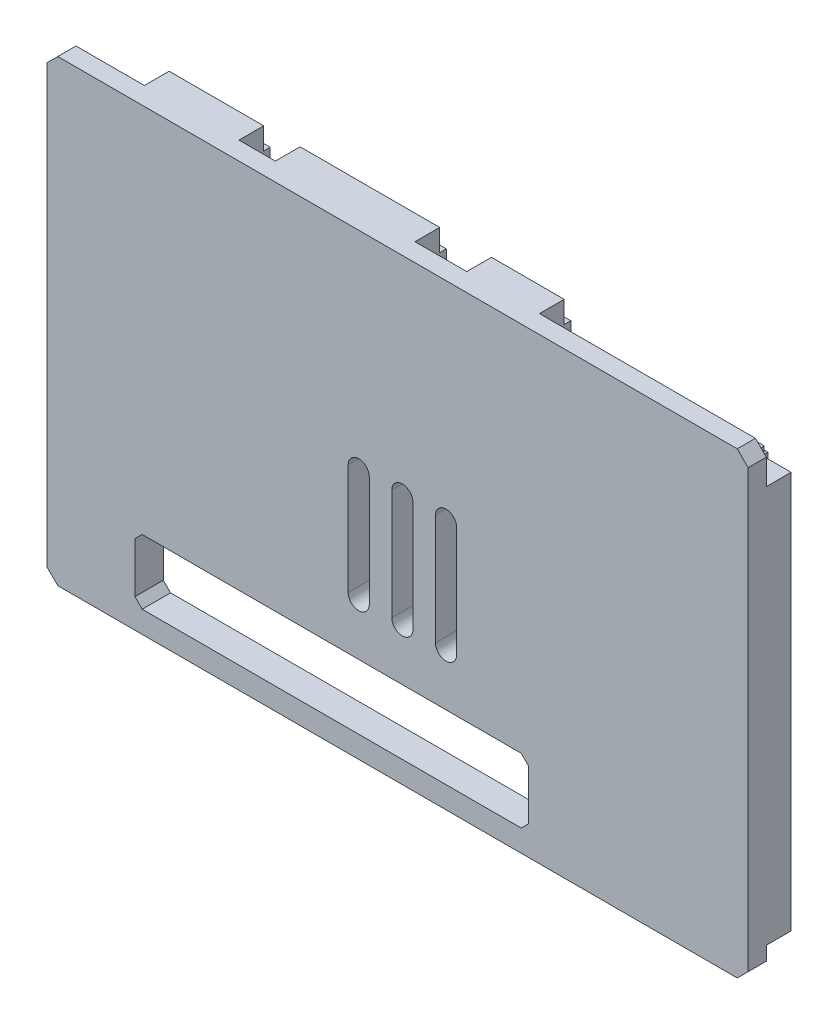
SolidWorks part; units mm, degrees
ref_plane "Front Plane" through (0, 0, 0) normal (0, 0, 1) x (1, 0, 0)
ref_plane "Top Plane" through (0, 0, 0) normal (0, 1, 0) x (1, 0, 0)
ref_plane "Right Plane" through (0, 0, 0) normal (1, 0, 0) x (0, 0, -1)
sketch "Sketch1" plane through (0, 0, 0) normal (0, 0, 1) x (1, 0, 0)
  line L1 (-38.1418, 30.0688) -> (58.2582, 30.0688)
  line L2 (-38.1418, 30.0688) -> (-38.1418, -32.9312)
  line L3 (-38.1418, -32.9312) -> (58.2582, -32.9312)
  line L4 (58.2582, 30.0688) -> (58.2582, -32.9312)
  line L5 (-36.4418, 28.3688) -> (56.5582, 28.3688)
  line L6 (-36.4418, 28.3688) -> (-36.4418, -31.2312)
  line L7 (-36.4418, -31.2312) -> (56.5582, -31.2312)
  line L8 (56.5582, 28.3688) -> (56.5582, -31.2312)
  line L9 (-31.6418, 27.0688) -> (55.2582, 27.0688)
  line L10 (-31.6418, 27.0688) -> (-31.6418, -29.9312)
  line L11 (-31.6418, -29.9312) -> (55.2582, -29.9312)
  line L12 (55.2582, 27.0688) -> (55.2582, -29.9312)
  dimension "D1" = 96.4
  dimension "D2" = 63
  dimension "D3" = 3
  dimension "D4" = 6.5
  dimension "D5" = 4.8
  dimension "D6" = 1.3
  dimension "D7" = 1.3
  dimension "D8" = 3
  dimension "D9" = 3
  dimension "D10" = 1.3
extrude "Boss-Extrude1" add sketch "Sketch1" along normal blind 2.5 contours L1 L4 L3 L2
extrude "Boss-Extrude2" add sketch "Sketch1<5>" against normal blind 1.4 contours L12 L9 L10 L11 | L8 L5 L6 L7 L9 L12 L11 L10 region at (10.0582, 27.2643, 0) region at (11.8082, -1.4312, 0)
sketch "Sketch1<5>" plane through (0, 0, 0) normal (0, 0, 1) x (1, 0, 0) same geometry as "Sketch1"
chamfer "Chamfer1" distance 1.5 angle 45 4 edges at (58.2582, 30.0688, 1.25) (-38.1418, 30.0688, 1.25) (-38.1418, -32.9312, 1.25) (58.2582, -32.9312, 1.25)
sketch "Sketch3" plane through (0, 0, -1.4) normal (0, 0, -1) x (-1, 0, 0)
  line L0 (36.4418, 28.3688) -> (36.4418, 28.1688)
  line L1 (36.4418, 28.3688) -> (36.4418, -31.2312) construction
  line L2 (36.4418, 28.1688) -> (36.4418, 5.3688)
  line L3 (36.4418, 5.3688) -> (36.4418, 4.9688)
  line L4 (36.4418, 4.9688) -> (38.1418, 4.9688)
  line L5 (38.1418, 4.9688) -> (38.1418, -8.2312)
  line L6 (38.1418, 28.5688) -> (38.1418, -31.4312) construction
  line L7 (36.4418, -8.2312) -> (36.4418, 4.9688)
  line L8 (36.6418, -32.9312) -> (-56.7582, -32.9312) construction
  line L9 (38.1418, 4.9688) -> (35.1418, 4.9688)
  line L10 (38.1418, 4.9688) -> (38.1418, -8.2312)
  line L11 (38.1418, -8.2312) -> (35.1418, -8.2312)
  line L12 (35.1418, 4.9688) -> (35.1418, -8.2312)
  line M5 (36.4418, -31.2312) -> (36.4418, 28.3688)
  dimension "D1" = 0.2
  dimension "D2" = 22.8
  dimension "D3" = 0.4
  dimension "D4" = 13.2
  dimension "D5" = 24.7
extrude "Boss-Extrude4" add sketch "Sketch3" against normal blind 1.7 contours L5 L4 M5 region at (-37.2918, -1.6312, -1.4)
sketch "Sketch4" plane through (0, 0, -1.4) normal (0, 0, -1) x (-1, 0, 0)
  line L0 (36.4418, 28.3688) -> (27.2418, 28.3688)
  line L1 (36.4418, 28.3688) -> (-56.5582, 28.3688) construction
  line L2 (27.2418, 28.3688) -> (14.2418, 28.3688)
  line L3 (14.2418, 28.3688) -> (9.2418, 28.3688)
  line L4 (9.2418, 28.3688) -> (-9.9582, 28.3688)
  line L5 (-9.9582, 28.3688) -> (-17.0682, 28.3688)
  line L6 (-17.0682, 28.3688) -> (-27.0682, 28.3688)
  line L8 (36.6418, 30.0688) -> (-56.7582, 30.0688) construction
  line L9 (-27.0682, 28.3688) -> (-17.0682, 28.3688)
  line L10 (-27.0682, 28.3688) -> (-27.0682, 30.0688)
  line L11 (-27.0682, 30.0688) -> (-17.0682, 30.0688)
  line L12 (-17.0682, 28.3688) -> (-17.0682, 30.0688)
  line L13 (-27.0682, 30.0688) -> (-17.0682, 30.0688)
  line L14 (-9.9582, 28.3688) -> (9.2418, 28.3688)
  line L15 (-9.9582, 28.3688) -> (-9.9582, 30.0688)
  line L16 (-9.9582, 30.0688) -> (9.2418, 30.0688)
  line L17 (9.2418, 28.3688) -> (9.2418, 30.0688)
  line L18 (14.2418, 28.3688) -> (27.2418, 28.3688)
  line L19 (14.2418, 28.3688) -> (14.2418, 30.0688)
  line L20 (14.2418, 30.0688) -> (27.2418, 30.0688)
  line L21 (27.2418, 28.3688) -> (27.2418, 30.0688)
  line L22 (-27.0682, 30.0688) -> (-27.0682, 27.0688)
  line L23 (-27.0682, 27.0688) -> (-17.0682, 27.0688)
  line L24 (-17.0682, 30.0688) -> (-17.0682, 27.0688)
  line L25 (-9.9582, 30.0688) -> (9.2418, 30.0688)
  line L26 (-9.9582, 30.0688) -> (-9.9582, 27.0688)
  line L27 (-9.9582, 27.0688) -> (9.2418, 27.0688)
  line L28 (9.2418, 30.0688) -> (9.2418, 27.0688)
  line L29 (14.2418, 30.0688) -> (27.2418, 30.0688)
  line L30 (14.2418, 30.0688) -> (14.2418, 27.0688)
  line L31 (14.2418, 27.0688) -> (27.2418, 27.0688)
  line L32 (27.2418, 30.0688) -> (27.2418, 27.0688)
  line M14 (36.4418, 28.3688) -> (-56.5582, 28.3688)
  dimension "D1" = 9.2
  dimension "D2" = 13
  dimension "D3" = 5
  dimension "D4" = 19.2
  dimension "D5" = 7.11
  dimension "D6" = 10
  dimension "D7" = 1.7
  dimension "D8" = 3
  dimension "D9" = 63.51
extrude "Boss-Extrude5" add sketch "Sketch4" against normal blind 1.6 contours L12 L11 L10 M14 | L17 L16 L15 M14 | L21 L20 L19 M14 region at (-20.7418, 29.2188, -1.4) region at (22.0682, 29.2188, -1.4) region at (0.3582, 29.2188, -1.4)
extrude "Boss-Extrude6" add sketch "Sketch4<3>" along normal blind 2 contours L12 L11 L10 M14 | L24 L22 L23 M14 | L28 L26 L27 M14 | L17 L16 L15 M14 | L32 L30 L31 M14 | L21 L20 L19 M14 region at (-20.7418, 27.7188, -1.4) region at (-20.7418, 29.2188, -1.4) region at (22.0682, 27.7188, -1.4) region at (22.0682, 29.2188, -1.4) region at (0.3582, 27.7188, -1.4) region at (0.3582, 29.2188, -1.4)
sketch "Sketch4<3>" plane through (0, 0, -1.4) normal (0, 0, -1) x (-1, 0, 0) same geometry as "Sketch4"
extrude "Boss-Extrude7" add sketch "Sketch3<5>" along normal blind 1 contours L9 L12 L11 M5 | L5 L4 M5 region at (-37.2918, -1.6312, -1.4) region at (-35.7918, -1.6312, -1.4)
sketch "Sketch3<5>" plane through (0, 0, -1.4) normal (0, 0, -1) x (-1, 0, 0) same geometry as "Sketch3"
sketch "Sketch5" plane through (0, 0, -1.4) normal (0, 0, -1) x (-1, 0, 0)
  line L0 (-56.5582, -32.9312) -> (-56.5582, -29.5312)
  line L1 (36.6418, -32.9312) -> (-56.7582, -32.9312) construction
  line L2 (-58.2582, -29.5312) -> (-56.5582, -29.5312)
  line L3 (-58.2582, 28.5688) -> (-58.2582, -31.4312) construction
  line L4 (-56.5582, -29.5312) -> (-56.5582, 25.0688)
  line L5 (-56.5582, 28.3688) -> (-56.5582, -31.2312) construction
  line L6 (-58.2582, -29.5312) -> (-55.2582, -29.5312)
  line L7 (-58.2582, -29.5312) -> (-56.5582, -29.5312)
  line L8 (-58.2582, -29.5312) -> (-58.2582, 25.0688)
  line L9 (-58.2582, 25.0688) -> (-56.5582, 25.0688)
  line L10 (-56.5582, -29.5312) -> (-56.5582, 25.0688)
  line L12 (-55.2582, -29.5312) -> (-58.2582, -29.5312)
  line L13 (-55.2582, -29.5312) -> (-55.2582, 25.0688)
  line L14 (-55.2582, 25.0688) -> (-58.2582, 25.0688)
  line L15 (-58.2582, -29.5312) -> (-58.2582, 25.0688)
  line M19 (-56.5582, 28.3688) -> (-56.5582, -31.2312)
  dimension "D1" = 3.4
  dimension "D2" = 54.6
extrude "Boss-Extrude8" add sketch "Sketch5" against normal blind 1.6 contours L9 L8 L2 M19 region at (57.4082, -2.2312, -1.4)
extrude "Boss-Extrude9" add sketch "Sketch5<3>" along normal blind 2 contours L13 L14 L6 M19 | L9 L8 L2 M19 region at (57.4082, -2.2312, -1.4) region at (55.9082, -2.2312, -1.4)
sketch "Sketch5<3>" plane through (0, 0, -1.4) normal (0, 0, -1) x (-1, 0, 0) same geometry as "Sketch5"
sketch "Sketch7" plane through (0, 0, 2.5) normal (0, 0, 1) x (1, 0, 0)
  line L0 (-36.6418, -32.9312) -> (56.7582, -32.9312) construction
  line L1 (-38.1418, -32.9312) -> (-26.0418, -32.9312)
  line L2 (-38.1418, -32.9312) -> (-38.1418, -29.9312)
  line L3 (-38.1418, -29.9312) -> (-26.0418, -29.9312)
  line L4 (-26.0418, -32.9312) -> (-26.0418, -29.9312)
  line L5 (-26.0418, -29.9312) -> (28.0582, -29.9312)
  line L6 (-26.0418, -29.9312) -> (-26.0418, -21.0312)
  line L7 (-26.0418, -21.0312) -> (28.0582, -21.0312)
  line L8 (28.0582, -29.9312) -> (28.0582, -21.0312)
  point P7 (-38.1418, -31.4312)
  point P8 (28.0582, -25.4812)
  dimension "D1" = 12.1
  dimension "D2" = 3
  dimension "D3" = 66.2
  dimension "D4" = 11.9
extrude "Cut-Extrude2" cut sketch "Sketch7" against normal blind 12 contours L5 L8 L7 L6 region at (1.0082, -25.4812, 2.5)
chamfer "Chamfer2" distance 1 angle 45 4 edges at (28.0582, -21.0312, 0.55) (28.0582, -29.9312, 0.55) (-26.0418, -29.9312, 0.55) (-26.0418, -21.0312, 0.55)
sketch "Sketch11" plane through (0, 27.0688, 0) normal (0, -1, 0) x (1, 0, 0)
  line L1 (17.0682, -3.4) -> (27.0682, -3.4)
  line L2 (17.0682, -3.4) -> (17.0682, -1.4)
  line L3 (17.0682, -1.4) -> (27.0682, -1.4)
  line L4 (27.0682, -3.4) -> (27.0682, -1.4)
  line L5 (-9.2418, -3.4) -> (9.9582, -3.4)
  line L6 (-9.2418, -3.4) -> (-9.2418, -1.4)
  line L7 (-9.2418, -1.4) -> (9.9582, -1.4)
  line L8 (9.9582, -3.4) -> (9.9582, -1.4)
  line L9 (-27.2418, -3.4) -> (-14.2418, -3.4)
  line L10 (-27.2418, -3.4) -> (-27.2418, -1.4)
  line L11 (-27.2418, -1.4) -> (-14.2418, -1.4)
  line L12 (-14.2418, -3.4) -> (-14.2418, -1.4)
extrude "Boss-Extrude10" add sketch "Sketch11" along normal blind 2
sketch "Sketch13" plane through (0, 0, -3.4) normal (0, 0, -1) x (-1, 0, 0)
  line L0 (-27.0682, 25.0688) -> (-27.0682, 28.3688) construction
  line L1 (-17.0682, 25.0688) -> (-27.0682, 25.0688)
  line L2 (-17.0682, 25.0688) -> (-17.0682, 27.0688)
  line L3 (-17.0682, 27.0688) -> (-27.0682, 27.0688)
  line L4 (-27.0682, 25.0688) -> (-27.0682, 27.0688)
  line L5 (-9.9582, 30.0688) -> (-9.9582, 25.0688) construction
  line L6 (9.2418, 25.0688) -> (-9.9582, 25.0688)
  line L7 (9.2418, 25.0688) -> (9.2418, 27.0688)
  line L8 (9.2418, 27.0688) -> (-9.9582, 27.0688)
  line L9 (-9.9582, 25.0688) -> (-9.9582, 27.0688)
  line L10 (14.2418, 28.3688) -> (14.2418, 25.0688) construction
  line L11 (27.2418, 25.0688) -> (14.2418, 25.0688)
  line L12 (27.2418, 25.0688) -> (27.2418, 27.0688)
  line L13 (27.2418, 27.0688) -> (14.2418, 27.0688)
  line L14 (14.2418, 25.0688) -> (14.2418, 27.0688)
extrude "Boss-Extrude12" add sketch "Sketch13" along normal blind 0.9
sketch "Sketch14" plane through (0, 0, -1.4) normal (0, 0, -1) x (-1, 0, 0)
  line L1 (-28.0582, -21.0312) -> (26.0418, -21.0312)
  line L2 (-28.0582, -21.0312) -> (-28.0582, -18.0312)
  line L3 (-28.0582, -18.0312) -> (26.0418, -18.0312)
  line L4 (26.0418, -21.0312) -> (26.0418, -18.0312)
extrude "Boss-Extrude13" add sketch "Sketch14" along normal blind 2.9
sketch "Sketch15" plane through (55.2582, 0, 0) normal (-1, 0, 0) x (0, 0, 1)
  line L1 (-3.4, 25.0688) -> (-1.4, 25.0688)
  line L2 (-3.4, 25.0688) -> (-3.4, -29.5312)
  line L3 (-3.4, -29.5312) -> (-1.4, -29.5312)
  line L4 (-1.4, 25.0688) -> (-1.4, -29.5312)
extrude "Boss-Extrude14" add sketch "Sketch15" along normal blind 4.5
sketch "Sketch16" plane through (0, 0, -3.4) normal (0, 0, -1) x (-1, 0, 0)
  line L0 (-50.7582, 25.0688) -> (-58.2582, 25.0688) construction
  line L1 (-50.7582, -29.5312) -> (-54.2582, -29.5312)
  line L2 (-50.7582, -29.5312) -> (-50.7582, 25.0688)
  line L3 (-50.7582, 25.0688) -> (-54.2582, 25.0688)
  line L4 (-54.2582, -29.5312) -> (-54.2582, 25.0688)
extrude "Boss-Extrude15" add sketch "Sketch16" along normal blind 0.8
sketch "Sketch17" plane through (0, 0, 2.5) normal (0, 0, 1) x (1, 0, 0)
  line L0 (-38.1418, -15.2312) -> (3.1582, -15.2312)
  line L1 (-38.1418, 28.5688) -> (-38.1418, -31.4312) construction
  line L2 (3.1582, -15.2312) -> (3.1582, -32.9312)
  line L3 (-36.6418, -32.9312) -> (56.7582, -32.9312) construction
  line L4 (4.7222, 1.4177) -> (4.7222, -13.7763) construction
  line L5 (6.1733, 1.4177) -> (6.1733, -13.7763)
  line L6 (3.2711, 1.4177) -> (3.2711, -13.7763)
  line L7 (10.7222, 1.4177) -> (10.7222, -13.7763) construction
  line L8 (12.1733, 1.4177) -> (12.1733, -13.7763)
  line L9 (9.2711, 1.4177) -> (9.2711, -13.7763)
  line L10 (16.7222, 1.4177) -> (16.7222, -13.7763) construction
  line L11 (18.1733, 1.4177) -> (18.1733, -13.7763)
  line L12 (15.2711, 1.4177) -> (15.2711, -13.7763)
  arc A0 (6.1733, 1.4177) -> (3.2711, 1.4177) centre (4.7222, 1.4177) ccw
  arc A1 (3.2711, -13.7763) -> (6.1733, -13.7763) centre (4.7222, -13.7763) ccw
  arc A2 (12.1733, 1.4177) -> (9.2711, 1.4177) centre (10.7222, 1.4177) ccw
  arc A3 (9.2711, -13.7763) -> (12.1733, -13.7763) centre (10.7222, -13.7763) ccw
  arc A4 (18.1733, 1.4177) -> (15.2711, 1.4177) centre (16.7222, 1.4177) ccw
  arc A5 (15.2711, -13.7763) -> (18.1733, -13.7763) centre (16.7222, -13.7763) ccw
  point P9 (4.7222, -6.1793)
  point P14 (4.7222, 2.8688)
  point P18 (10.7222, -6.1793)
  point P25 (16.7222, -6.1793)
  dimension "D4" = 3
  dimension "D1" = 41.3
  dimension "D2" = 17.7
  dimension "D3" = 35.8
extrude "Cut-Extrude3" cut sketch "Sketch17" against normal blind 10 contours L6 A1 L5 A0 | L12 A5 L11 A4 | L9 A3 L8 A2 region at (4.7222, -6.1793, 2.5) region at (10.7222, -6.1793, 2.5) region at (16.7222, -6.1793, 2.5)
